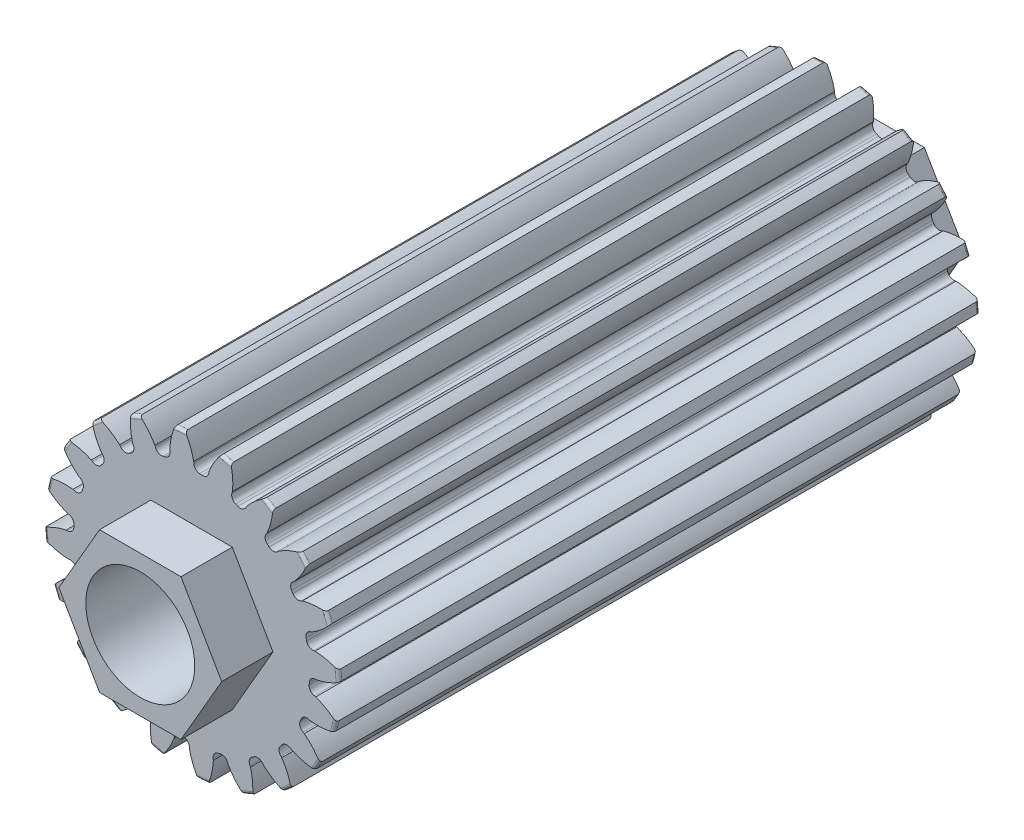
SolidWorks part; units mm, degrees
material "ABS"
ref_plane "Front" through (0, 0, 0) normal (0, 0, 1) x (1, 0, 0)
ref_plane "Top" through (0, 0, 0) normal (0, 1, 0) x (1, 0, 0)
ref_plane "Right" through (0, 0, 0) normal (1, 0, 0) x (0, 0, -1)
sketch "Sketch1" plane through (0, 0, 0) normal (0, 0, 1) x (1, 0, 0)
  line L0 (-254, 0) -> (254, 0) construction
  circle A0 centre (0, 0) radius 8.763
  circle A1 centre (0, 0) radius 7.9375 construction
  circle A3 centre (0, 0) radius 7.0191 construction
  dimension "D1" = 0.9184
  dimension "D2" = 1.7439
  dimension "D3" = 0.8255
extrude "Boss-Extrude1" add sketch "Sketch1" against normal blind 38.1
sketch "Sketch2" plane through (0, 0, 0) normal (1, 0, 0) x (0, 0, -1)
  line L0 (4.7625, 0) -> (11.1252, 0)
  line L1 (4.7625, 0) -> (4.7625, 5.9531)
  line L2 (4.7625, 5.9531) -> (11.1252, 5.9531)
  line L3 (11.1252, 5.9531) -> (11.1252, 0)
  point P5 (11.1252, -5.9531)
  point P6 (0, -8.763)
  point P7 (38.1, -8.763)
  point P9 (0, 8.763)
revolve "Revolve1" add sketch "Sketch2" angle 360 mid plane about L0
fillet "Fillet2" radius 0.1753 2 edges at (8.763, 0, -38.1) (8.763, 0, 0)
sketch "Sketch3" plane through (0, 0, 0) normal (0, 0, 1) x (1, 0, 0)
  line L0 (0, 0) -> (0, 8.763) construction
  line L1 (-2.5511, 7.009) -> (0, 7.9375)
  line L2 (-9.5921, 7.9375) -> (9.5921, 7.9375) construction
  line L3 (-9.0136, 4.6568) -> (9.0136, 11.2182) construction
  line L4 (-2.5511, 7.009) -> (0, 0) construction
  line L5 (-6.2194, 4.1174) -> (0, 0) construction
  line L6 (-6.2194, 4.1174) -> (-2.0982, 10.3425) construction
  line L7 (-1.7721, 7.2452) -> (0, 0) construction
  line L8 (-1.7721, 7.2452) -> (0.0739, 7.6967) construction
  arc A0 (-2.5511, 7.009) -> (-6.2194, 4.1174) centre (0, 0) ccw
  circle A1 centre (0, 0) radius 7.9375 construction
  circle A2 centre (0, 0) radius 7.4588 construction
  arc A3 (-2.5511, 7.009) -> (-1.7721, 7.2452) centre (0, 0) cw
  circle A4 centre (0, 0) radius 8.763 construction
  point P6 (0, 7.9375)
  dimension "D1" = 2.7148
  dimension "D3" = 7.4657
  dimension "D5" = 1.9003
  dimension "D2" = 4.7509
  dimension "D4" = 0.8144
sketch "Sketch4" plane through (0, 0, 0) normal (0, 0, 1) x (1, 0, 0)
  line L0 (0, 0) -> (0.6209, 7.8886) construction
  line L1 (0.1318, 7.4576) -> (0.1318, 7.0179)
  line L2 (0, 7.9375) -> (1.2417, 7.8398) construction
  line L3 (1.0365, 7.3864) -> (0.9677, 6.9521)
  line L4 (0.1318, 7.0179) -> (0, 0) construction
  line L5 (0, 0) -> (0, 8.763) construction
  line L6 (-6.2194, 4.1174) -> (-2.0982, 10.3425) construction
  line L7 (-6.2194, 4.1174) -> (-2.0982, 10.3425) construction
  arc A0 (0.9677, 6.9521) -> (0.1318, 7.0179) centre (0, 0) ccw
  arc A1 (0, 7.9375) -> (1.2417, 7.8398) centre (0, 0) cw construction
  circle A2 centre (0, 0) radius 7.9375 construction
  circle A3 centre (0, 0) radius 7.4588 construction
  circle A4 centre (0, 0) radius 7.0191 construction
  arc A5 (3.6903, 9.8869) -> (-2.0982, 10.3425) centre (0, 0) ccw
  spline S0 degree 2 poles (-2.0982, 10.3425) (-0.2509, 9.2652) (0.1318, 7.4576) knots 0 0 0 1 1 1
  spline S1 degree 2 poles (3.6903, 9.8869) (1.6972, 9.1118) (1.0365, 7.3864) knots 0 0 0 1 1 1
  dimension "D1" = 1.2468
extrude "Cut-Extrude1" cut sketch "Sketch4" against normal through all
fillet "Fillet1" radius 0.374 2 edges at (0.9677, 6.9521, -19.05) (0.1318, 7.0179, -19.05)
pattern_circular "CirPattern1" count 20 over 360 about axis through (0, 0, -38.1) along (0, 0, 1) of "Cut-Extrude1", "Fillet1"
sketch "Sketch5" plane through (0, 0, 0) normal (0, 0, 1) x (1, 0, 0)
  circle A0 centre (0, 0) radius 2.3813
  circle A1 centre (0, 0) radius 2.3813 construction
  dimension "Bore Min" = 4.7625
  dimension "Bore Max" = 4.7625
extrude "Cut-Extrude2" cut sketch "Sketch5" against normal through all
chamfer "Chamfer1" [suppressed] distance 0.2977 angle 45
sketch "Pitch Dia" plane through (0, 0, 0) normal (0, 0, 1) x (1, 0, 0)
  circle A0 centre (0, 0) radius 7.9375 construction
  circle A1 centre (0, 0) radius 7.9375 construction
sketch "Sketch6" [suppressed] plane through (0, 0, -11.1252) normal (0, 0, -1) x (-1, 0, 0)
  circle A0 centre (0, 0) radius 6.35
  dimension "D1" = 12.7
extrude "Cut-Extrude3" [suppressed] cut sketch "Sketch6" against normal blind 4.7752
sketch "Sketch8" plane through (0, 0, 0) normal (0, 0, 1) x (1, 0, 0)
  circle A0 centre (0, 0) radius 3.2385
  dimension "D1" = 6.477
extrude "Cut-Extrude4" cut sketch "Sketch8" against normal through all
sketch "Sketch9" plane through (0, 0, -38.1) normal (0, 0, -1) x (-1, 0, 0)
  line L1 (2.4197, 4.191) -> (-2.4197, 4.191)
  line L2 (-2.4197, 4.191) -> (-4.8393, 0)
  line L3 (-4.8393, 0) -> (-2.4197, -4.191)
  line L4 (-2.4197, -4.191) -> (2.4197, -4.191)
  line L5 (2.4197, -4.191) -> (4.8393, 0)
  line L6 (4.8393, 0) -> (2.4197, 4.191)
  circle A0 centre (0, 0) radius 4.191 construction
  circle A1 centre (0, 0) radius 3.2385
  dimension "D1" = 8.382
  dimension "D2" = 6.477
extrude "Boss-Extrude2" add sketch "Sketch9" along normal blind 3.048
sketch "Sketch10" plane through (0, 0, 0) normal (0, 0, 1) x (1, 0, 0)
  line L1 (2.4197, 4.191) -> (-2.4197, 4.191)
  line L2 (-2.4197, 4.191) -> (-4.8393, 0)
  line L3 (-4.8393, 0) -> (-2.4197, -4.191)
  line L4 (-2.4197, -4.191) -> (2.4197, -4.191)
  line L5 (2.4197, -4.191) -> (4.8393, 0)
  line L6 (4.8393, 0) -> (2.4197, 4.191)
  circle A0 centre (0, 0) radius 4.191 construction
  circle A1 centre (0, 0) radius 3.2385
  dimension "D1" = 8.382
  dimension "D2" = 6.477
extrude "Boss-Extrude3" add sketch "Sketch10" along normal blind 3.048
equation "\"D1@Boss-Extrude1\"=\"Face Wd@Sketch2\"+.0625"
equation "\"D2@Sketch3\" = \"D1@Sketch3\"*1.75"
equation "\"D3@Sketch3\" = \"D1@Sketch3\"+\"D2@Sketch3\""
equation "\"D4@Sketch3\" = \"D1@Sketch3\"*.3"
equation "\"D5@Sketch3\" = \"D1@Sketch3\"-\"D4@Sketch3\""
equation "\"D1@Sketch4\" = 1.5708/(\"Number of Teeth@Sketch1\"/\"Ptich Dia@Sketch1\")"
equation "\"D1@Chamfer1\" = \"B Hub Dia@Sketch2\"*.025"
equation "\"D1@CirPattern1\" = \"Number of Teeth@Sketch1\""
equation "\"D1@Fillet1\" = \"D1@Sketch4\"*.3"
equation "\"D1@Fillet2\" = \"OD@Sketch1\"*.01"
equation "\"D1@Sketch1\" = 1.157/(\"Number of Teeth@Sketch1\"/\"Ptich Dia@Sketch1\")"
